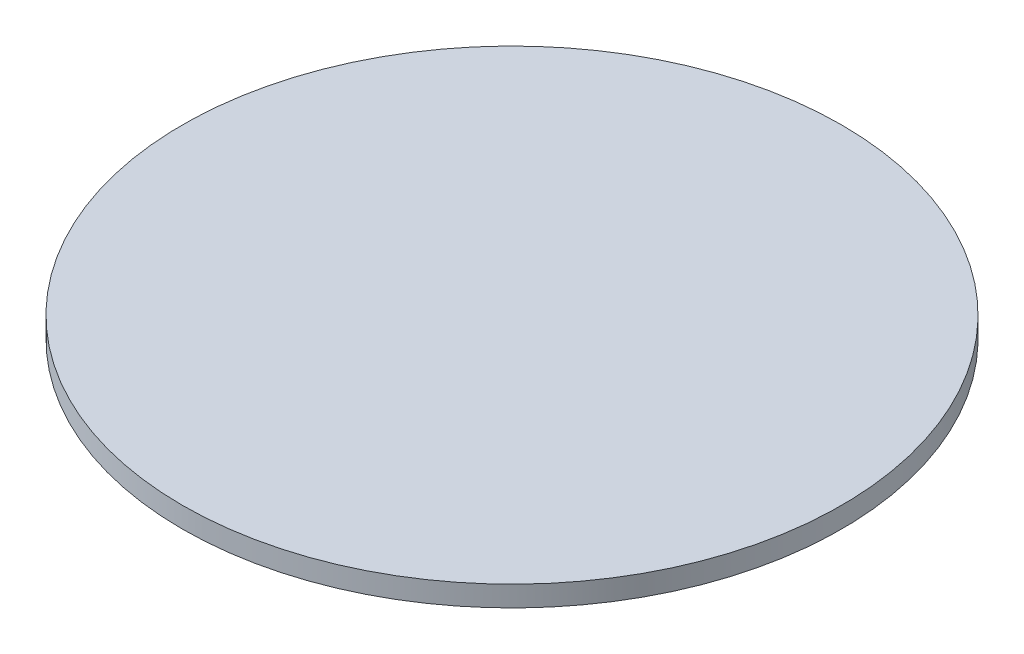
SolidWorks part; units mm, degrees
ref_plane "Front Plane" through (0, 0, 0) normal (0, 0, 1) x (1, 0, 0)
ref_plane "Top Plane" through (0, 0, 0) normal (0, 1, 0) x (1, 0, 0)
ref_plane "Right Plane" through (0, 0, 0) normal (1, 0, 0) x (0, 0, -1)
sketch "Sketch1" plane through (0, 0, 0) normal (0, 1, 0) x (1, 0, 0)
  circle A0 centre (0, 0) radius 101.6
  dimension "D1" = 203.2
extrude "Boss-Extrude1" add sketch "Sketch1" against normal blind 6.35
